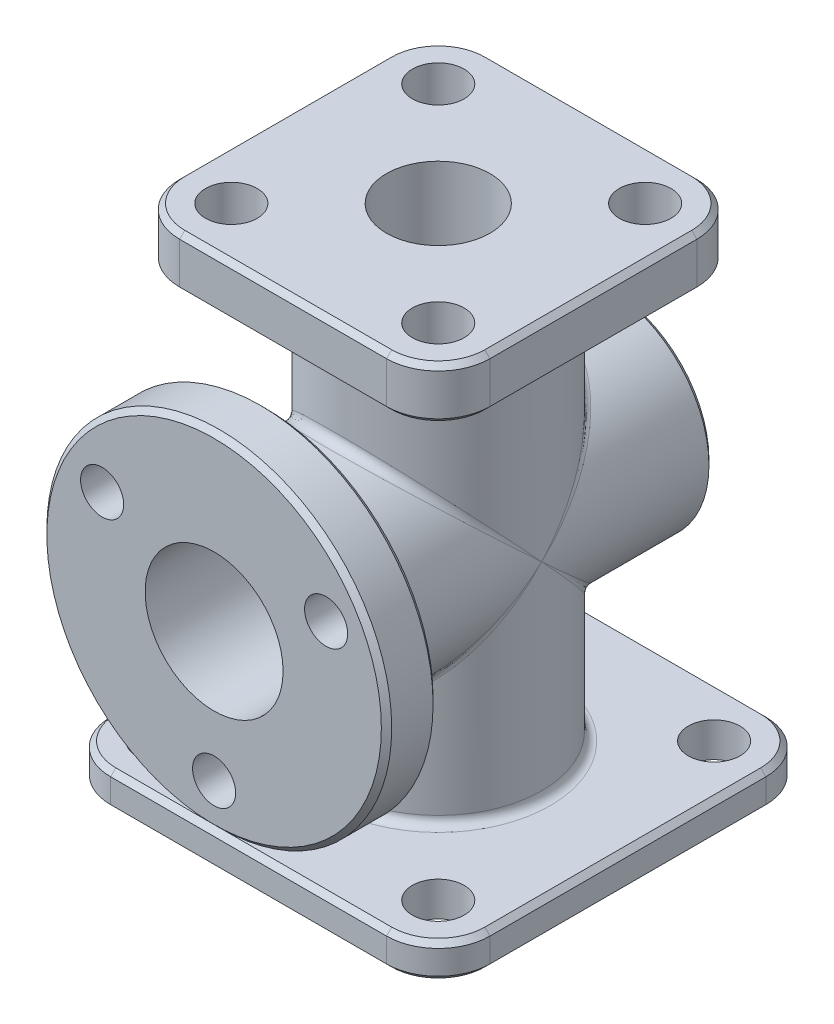
SolidWorks part; units mm, degrees
ref_plane "Front Plane" through (0, 0, 0) normal (0, 0, 1) x (1, 0, 0)
ref_plane "Top Plane" through (0, 0, 0) normal (0, 1, 0) x (1, 0, 0)
ref_plane "Right Plane" through (0, 0, 0) normal (1, 0, 0) x (0, 0, -1)
sketch "Sketch1" plane through (0, 0, 0) normal (0, 1, 0) x (1, 0, 0)
  line L1 (6, -9) -> (-6, -9)
  line L2 (9, -6) -> (9, 6)
  line L3 (6, 9) -> (-6, 9)
  line L4 (-9, -6) -> (-9, 6)
  line L5 (9, -9) -> (-9, 9) construction
  line L6 (9, 9) -> (-9, -9) construction
  arc A0 (6, -9) -> (9, -6) centre (6, -6) ccw
  arc A1 (-6, -9) -> (-9, -6) centre (-6, -6) cw
  arc A2 (9, 6) -> (6, 9) centre (6, 6) ccw
  arc A3 (-6, 9) -> (-9, 6) centre (-6, 6) ccw
  circle A4 centre (-6, 6) radius 1.5
  circle A5 centre (6, 6) radius 1.5
  circle A6 centre (6, -6) radius 1.5
  circle A7 centre (-6, -6) radius 1.5
  point P0 (0, 0)
  dimension "D3" = 3
  dimension "D4" = 3
  dimension "D1" = 18
  dimension "D2" = 18
extrude "Boss-Extrude1" add sketch "Sketch1" along normal blind 3
sketch "Sketch2" plane through (0, 0, 0) normal (0, 1, 0) x (1, 0, 0)
  circle A0 centre (0, 0) radius 6
  dimension "D1" = 12
extrude "Boss-Extrude2" add sketch "Sketch2" against normal blind 24
sketch "Sketch3" plane through (0, -24, 0) normal (0, -1, 0) x (1, 0, 0)
  line L1 (8, -11) -> (-8, -11)
  line L2 (11, -8) -> (11, 8)
  line L3 (8, 11) -> (-8, 11)
  line L4 (-11, -8) -> (-11, 8)
  line L5 (11, -11) -> (-11, 11) construction
  line L6 (11, 11) -> (-11, -11) construction
  arc A0 (8, -11) -> (11, -8) centre (8, -8) ccw
  arc A1 (-8, -11) -> (-11, -8) centre (-8, -8) cw
  arc A2 (11, 8) -> (8, 11) centre (8, 8) ccw
  arc A3 (-8, 11) -> (-11, 8) centre (-8, 8) ccw
  circle A4 centre (-8, 8) radius 1.5
  circle A5 centre (8, 8) radius 1.5
  circle A6 centre (8, -8) radius 1.5
  circle A7 centre (-8, -8) radius 1.5
  point P0 (0, 0)
  dimension "D3" = 3
  dimension "D4" = 3
  dimension "D1" = 22
  dimension "D2" = 22
extrude "Boss-Extrude3" add sketch "Sketch3" along normal blind 2
sketch "Sketch4" plane through (0, 3, 0) normal (0, 1, 0) x (1, 0, 0)
  circle A0 centre (0, 0) radius 3
  dimension "D1" = 6
extrude "Cut-Extrude1" cut sketch "Sketch4" against normal through all
chamfer "Chamfer1" distance 3 angle 45 1 edges at (0, -26, 3)
sketch "Sketch5" plane through (0, 0, 0) normal (0, 0, 1) x (1, 0, 0)
  line L0 (8, -26) -> (-8, -26) construction
  circle A0 centre (0, -12) radius 6
  point P4 (0, 0)
  dimension "D1" = 12
  dimension "D2" = 14
extrude "Boss-Extrude4" add sketch "Sketch5" along normal mid plane 20
sketch "Sketch6" plane through (0, 0, 10) normal (0, 0, 1) x (1, 0, 0)
  line L0 (0, -4.5) -> (0, -12) construction
  line L1 (0, -12) -> (-6.4952, -8.25) construction
  circle A0 centre (0, -12) radius 10
  circle A1 centre (0, -12) radius 7.5 construction
  circle A2 centre (-6.4952, -8.25) radius 1.25
  circle A3 centre (6.4952, -8.25) radius 1.25
  circle A4 centre (0, -12) radius 7.5 construction
  circle A5 centre (0, -19.5) radius 1.25
  circle A6 centre (0, -12) radius 7.5 construction
  point P16 (0, -12)
  dimension "D1" = 20
  dimension "D2" = 15
  dimension "D3" = 2.5
  dimension "D4" = 60
  dimension "D5" = 3
extrude "Boss-Extrude5" add sketch "Sketch6" along normal blind 3
sketch "Sketch7" plane through (0, 0, 13) normal (0, 0, 1) x (1, 0, 0)
  circle A0 centre (0, -12) radius 4
  dimension "D1" = 8
extrude "Cut-Extrude2" cut sketch "Sketch7" against normal blind 19
sketch "Sketch8" plane through (0, 0, -10) normal (0, 0, -1) x (-1, 0, 0)
  circle A0 centre (0, -12) radius 1.5
  dimension "D1" = 3
extrude "Cut-Extrude3" cut sketch "Sketch8" against normal through all
fillet "Fillet1" radius 0.5 6 edges at (0, 0, 6) (0, -24, 6) (0, -18, 6) (0, -18, -6) (0, -6, -6) (0, -6, 6)
chamfer "Chamfer2" distance 0.3 angle 45 35 edges at (6, -12, -10) (9, 0, 0) (8.1213, 0, -8.1213) (8.1213, 0, 8.1213) (0, 0, -9) (0, 0, 9) (-8.1213, 0, -8.1213) (-8.1213, 0, 8.1213) (-9, 0, 0) (9, 3, 0) (8.1213, 3, -8.1213) (8.1213, 3, 8.1213) (0, 3, -9) (0, 3, 9) (-8.1213, 3, -8.1213) (-8.1213, 3, 8.1213) (-9, 3, 0) (11, -26, 0) (10.1213, -26, 10.1213) (10.1213, -26, -10.1213) (0, -26, 11) (0, -26, -11) (-10.1213, -26, 10.1213) (-10.1213, -26, -10.1213) (-11, -26, 0) (11, -24, 0) (10.1213, -24, 10.1213) (10.1213, -24, -10.1213) (0, -24, 11) (0, -24, -11) (-10.1213, -24, 10.1213) (-10.1213, -24, -10.1213) (-11, -24, 0) (10, -12, 10) (10, -12, 13)
